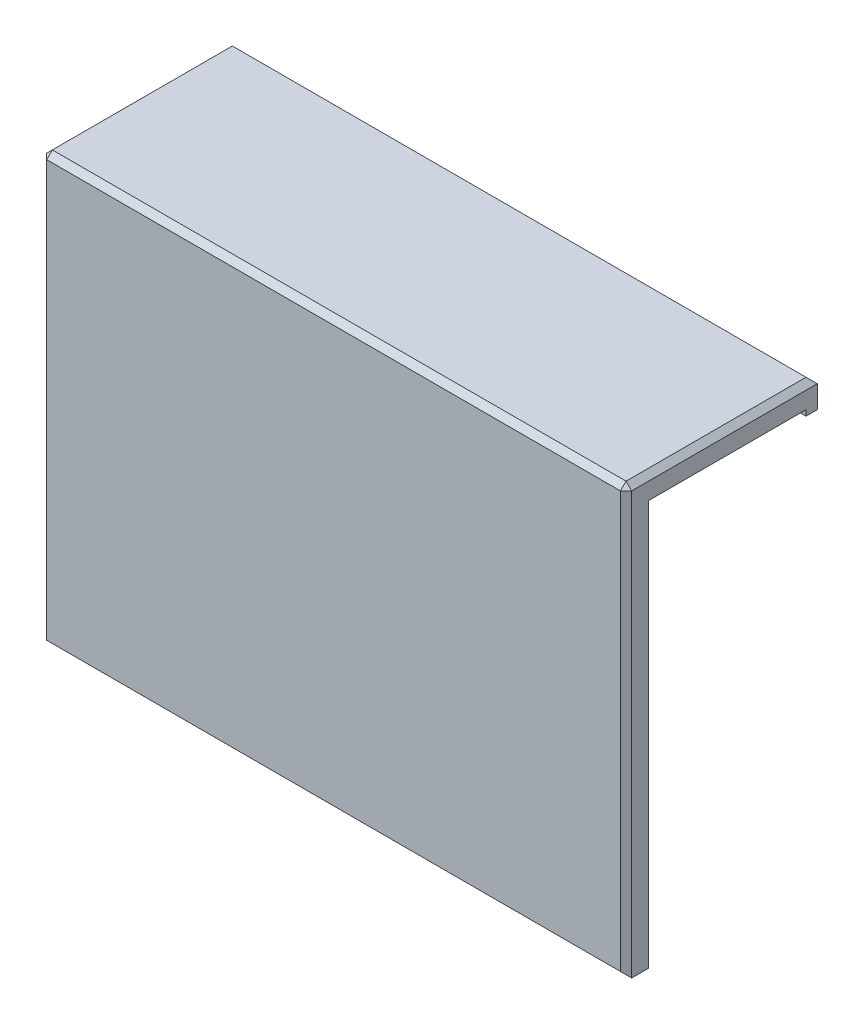
SolidWorks part; units mm, degrees
ref_plane "Front Plane" through (0, 0, 0) normal (0, 0, 1) x (1, 0, 0)
ref_plane "Top Plane" through (0, 0, 0) normal (0, 1, 0) x (1, 0, 0)
ref_plane "Right Plane" through (0, 0, 0) normal (1, 0, 0) x (0, 0, -1)
sketch "Sketch1" plane through (0, 0, 0) normal (0, 0, 1) x (1, 0, 0)
  line L0 (-2, -2) -> (-2, 74)
  line L1 (0, 0) -> (100, 0)
  line L2 (0, 0) -> (0, 72)
  line L3 (0, 72) -> (100, 72)
  line L4 (100, 0) -> (100, 72)
  line L5 (-2, 74) -> (102, 74)
  line L6 (102, -2) -> (102, 74)
  line L7 (-2, -2) -> (102, -2)
  line L8 (100, 0) -> (102, 0)
  line L9 (0, 0) -> (-2, 0)
  dimension "D1" = 72
  dimension "D2" = 100
  dimension "D3" = 2
extrude "Boss-Extrude1" add sketch "Sketch1" along normal blind 1 contours L1 L4 L3 L2 | L0 L7 L6 L5 L4 L1 L2 L3 region at (-0.7236, 37, 0) region at (50, 36, 0)
extrude "Boss-Extrude2" add sketch "Sketch1<3>" against normal blind 3 contours L9 L2 L3 L4 L8 L6 L5 L0 region at (-0.7236, 37, 0)
sketch "Sketch1<3>" plane through (0, 0, 0) normal (0, 0, 1) x (1, 0, 0) same geometry as "Sketch1"
sketch "Sketch2" plane through (0, 0, -3) normal (0, 0, -1) x (-1, 0, 0)
  line L0 (-102, 74) -> (2, 74)
  line L4 (2, 74) -> (2, 70)
  line L5 (2, 70) -> (0, 70)
  line L7 (0, 70) -> (0, 72)
  line L8 (0, 72) -> (-100, 72)
  line L10 (-100, 72) -> (-100, 70)
  line L12 (-100, 70) -> (-102, 70)
  line L13 (-102, 70) -> (-102, 74)
  dimension "D1" = 4
  dimension "D2" = 2
extrude "Boss-Extrude3" add sketch "Sketch2" along normal blind 28
sketch "Sketch3" plane through (0, 0, 0) normal (0, -1, 0) x (1, 0, 0)
  line L0 (-2, 1) -> (-2, -3) construction
  line L1 (-2, 1) -> (102, 1)
  line L2 (-2, 1) -> (-2, -3)
  line L3 (-2, -3) -> (102, -3)
  line L4 (102, 1) -> (102, -3)
  line L5 (-2, 1) -> (102, 1) construction
  line L6 (102, 1) -> (102, -3) construction
  dimension "D1" = 4
extrude "Boss-Extrude4" add sketch "Sketch3" along normal blind 2
sketch "Sketch4" plane through (-2, 0, 0) normal (-1, 0, 0) x (0, 0, 1)
  line L0 (-3, 0) -> (0.2, 0)
  line L2 (-3, -2) -> (-3, 70) construction
  arc A0 (0.2, 0) -> (-2.2, 0) centre (-1, 0) cw
  point P8 (0, 0)
  dimension "D2" = 1.2
  dimension "D1" = 3.2
extrude "Cut-Extrude1" cut sketch "Sketch4" against normal blind 11 and the other way blind 11 from offset 52 contours A0 L0 region at (-2, -0.5093, -1) offset against normal yes
sketch "Sketch5" plane through (0, 0, -31) normal (0, 0, -1) x (-1, 0, 0)
  line L0 (-102, 74) -> (-102, 70) construction
  line L1 (-102, 74) -> (2, 74)
  line L2 (-102, 74) -> (-102, 69)
  line L3 (-102, 69) -> (2, 69)
  line L4 (2, 74) -> (2, 69)
  line L5 (2, 70) -> (2, 74) construction
  line L6 (2, 74) -> (-102, 74) construction
  dimension "D1" = 5
extrude "Boss-Extrude6" add sketch "Sketch5" along normal blind 2
sketch "Sketch6" plane through (-2, 0, 0) normal (-1, 0, 0) x (0, 0, 1)
  line L0 (-31, 69) -> (-31, 72.2)
  line L1 (-31, 69) -> (-31, 70) construction
  line L2 (-33, 69) -> (-31, 69) construction
  arc A0 (-31, 72.2) -> (-31, 69.8) centre (-31, 71) ccw
  dimension "D2" = 1.2
  dimension "D1" = 3.2
extrude "Cut-Extrude2" cut sketch "Sketch6" along normal blind 11 from offset 32 contours L0 A0 region at (-2, 71, -31.5093) offset against normal yes
extrude "Cut-Extrude3" cut sketch "Sketch6<3>" against normal blind 11 from offset 72 contours L0 A0 region at (-2, 71, -31.5093) offset against normal yes
sketch "Sketch6<3>" plane through (-2, 0, 0) normal (-1, 0, 0) x (0, 0, 1) same geometry as "Sketch6"
chamfer "Chamfer2" distance 1 angle 45 7 edges at (50, 74, -33) (50, 74, 1) (-2, 74, -16) (-2, 36, 1) (50, -2, 1) (102, 36, 1) (102, 74, -16)
